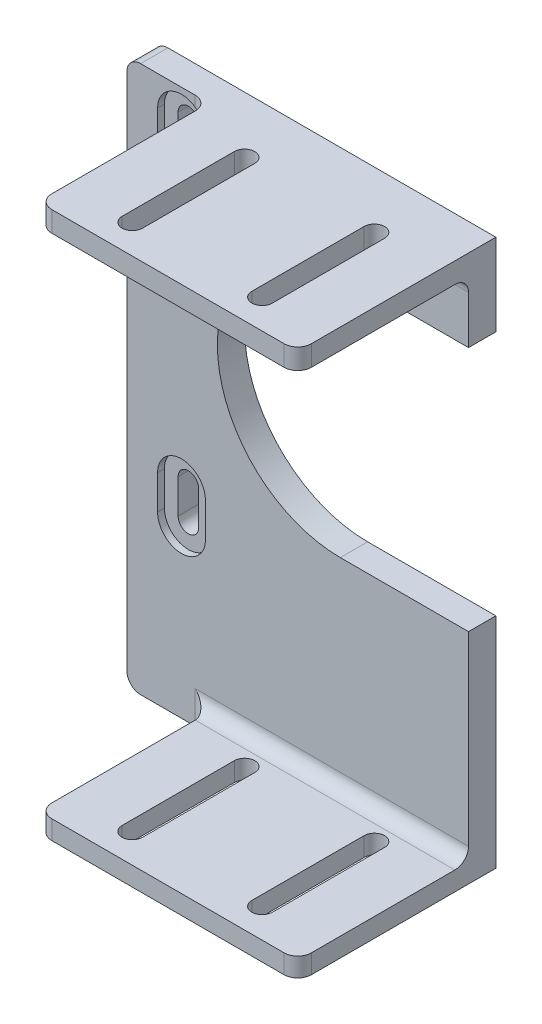
SolidWorks part; units mm, degrees
ref_plane "Front Plane" through (0, 0, 0) normal (0, 0, 1) x (1, 0, 0)
ref_plane "Top Plane" through (0, 0, 0) normal (0, 1, 0) x (1, 0, 0)
ref_plane "Right Plane" through (0, 0, 0) normal (1, 0, 0) x (0, 0, -1)
sketch "Sketch1" plane through (0, 0, 0) normal (0, 0, 1) x (1, 0, 0)
  line L19 (1779.3375, 22.373) -> (1779.3375, -22.3731) construction
  line L20 (1788.3589, -31.3946) -> (1832.7922, -31.3946) construction
  line L21 (1841.8136, -22.3731) -> (1841.8136, 22.373) construction
  line L22 (1832.7922, 31.3944) -> (1788.3589, 31.3944) construction
  line L23 (1853.7515, -14.8225) -> (1846.3832, -11.8988) construction
  line L24 (1779.3375, 22.373) -> (1779.3375, -22.3731) construction
  line L25 (1788.3589, -31.3946) -> (1832.7922, -31.3946) construction
  line L26 (1841.8136, -22.3731) -> (1841.8136, 22.373) construction
  line L27 (1832.7922, 31.3944) -> (1788.3589, 31.3944) construction
  line L28 (1853.7515, -14.8225) -> (1846.3832, -11.8988) construction
  line L29 (1788.3589, -29.8946) -> (1832.7922, -29.8946)
  line L30 (1840.3136, -22.3731) -> (1840.3136, 22.373)
  line L31 (1832.7922, 29.8944) -> (1788.3589, 29.8944)
  line L32 (1829.3375, -18) -> (1829.3375, -29.8946)
  line L33 (1810.5755, 18) -> (1829.3375, 18)
  line L34 (1779.3375, 0) -> (1779.3375, -50)
  line L35 (1779.3375, 0) -> (1829.3375, 0)
  line L36 (1779.3375, -50) -> (1829.3375, -50)
  line L37 (1829.3375, 0) -> (1829.3375, -50)
  line L38 (1810.5755, -18) -> (1829.3375, -18)
  line L39 (1779.3375, 0) -> (1829.3375, 0)
  line L40 (1779.3375, 0) -> (1779.3375, 30)
  line L41 (1779.3375, 30) -> (1829.3375, 30)
  line L42 (1829.3375, 0) -> (1829.3375, 30)
  line L43 (1829.3375, -29.8946) -> (1788.3589, -29.8946)
  arc A10 (1826.4876, 1.6748) -> (1820.1851, -12.7928) centre (1810.5755, 0) ccw construction
  arc A11 (1851.9074, -19.47) -> (1853.7515, -14.8225) centre (1852.8295, -17.1462) ccw construction
  arc A12 (1826.4876, 1.6748) -> (1820.1851, -12.7928) centre (1810.5755, 0) ccw construction
  arc A13 (1851.9074, -19.47) -> (1853.7515, -14.8225) centre (1852.8295, -17.1462) ccw construction
  circle A14 centre (1787.3272, -23.7436) radius 1.5 construction
  circle A15 centre (1787.3272, -23.7436) radius 1.5 construction
  circle A16 centre (1833.8238, -23.7436) radius 1.5 construction
  circle A17 centre (1833.8238, -23.7436) radius 1.5 construction
  circle A18 centre (1833.8238, 23.1061) radius 1.5 construction
  circle A19 centre (1787.3272, 23.1061) radius 1.5
  circle A20 centre (1787.3272, 23.1061) radius 1.5 construction
  circle A21 centre (1833.8238, 23.1061) radius 1.5 construction
  arc A22 (1828.4766, 1.8842) -> (1821.3863, -14.3919) centre (1810.5755, 0) ccw
  parabola Q1 (1842.8609, -10.1768) -> (1826.4876, 1.6748) focus (1827.8677, 2.7392) apex (1826.418, 2.9721) construction
  parabola Q2 (1842.8609, -10.1768) -> (1826.4876, 1.6748) focus (1827.8677, 2.7392) apex (1826.418, 2.9721) construction
  spline S6 degree 3 poles (2125.9154, -960.3929) (1827.9786, 38.5022) (1774.078, -7.1663) (1780.1758, -26.4625) (1781.8315, -28.9006) (1784.2696, -30.5564) (1803.5659, -36.6543) (1849.2336, 17.2492) (850.3625, 315.1978) knots -0.087298 -0.087298 -0.087298 -0.087298 0.347222 0.361111 0.388889 0.416667 0.430556 0.865087 0.865087 0.865087 0.865087 only from (1779.3375, -22.3731) to (1788.3589, -31.3946) construction
  spline S7 degree 3 poles (2770.8029, 315.202) (1771.9171, 17.2497) (1817.5852, -36.6543) (1836.8816, -30.5564) (1839.3196, -28.9006) (1840.9754, -26.4625) (1847.0731, -7.1664) (1793.1728, 38.502) (1495.2376, -960.3866) knots 0.134911 0.134911 0.134911 0.134911 0.569444 0.583333 0.611111 0.638889 0.652778 1.087297 1.087297 1.087297 1.087297 only from (1832.7922, -31.3946) to (1841.8136, -22.3731) construction
  spline S8 degree 3 poles (1495.1659, 960.3676) (1793.1635, -38.5025) (1847.0736, 7.165) (1840.9754, 26.4623) (1839.3196, 28.9004) (1836.8816, 30.5561) (1817.5851, 36.6542) (1771.9171, -17.251) (2770.7955, -315.2292) knots -0.06356 -0.06356 -0.06356 -0.06356 0.805556 0.833333 0.888889 0.944444 0.972222 1.841293 1.841293 1.841293 1.841293 only from (1841.8136, 22.373) to (1832.7922, 31.3944) construction
  spline S9 degree 3 poles (850.3593, -315.2281) (1849.2339, -17.2509) (1803.5661, 36.6542) (1784.2696, 30.5561) (1781.8315, 28.9004) (1780.1758, 26.4623) (1774.0775, 7.165) (1827.9875, -38.5023) (2125.9836, 960.362) knots -0.309535 -0.309535 -0.309535 -0.309535 0.125 0.138889 0.166667 0.194444 0.208333 0.64289 0.64289 0.64289 0.64289 only from (1788.3589, 31.3944) to (1779.3375, 22.373) construction
  spline S10 degree 3 poles (1294.2263, 837.7139) (2450.569, -777.537) (1082.9552, 664.1035) (2665.885, -600.3447) knots -3.232046 -3.232046 -3.232046 -3.232046 3.445011 3.445011 3.445011 3.445011 only from (1820.1851, -12.7928) to (1851.9074, -19.47) construction
  spline S11 degree 3 poles (2833.4468, -172.2254) (835.6889, 37.6788) (2800.9395, 103.594) (867.7165, -231.7317) knots -2.34656 -2.34656 -2.34656 -2.34656 4.307168 4.307168 4.307168 4.307168 only from (1846.3832, -11.8988) to (1842.8609, -10.1768) construction
  spline S12 degree 3 poles (1779.3375, -22.3731) (1779.3375, -22.9801) (1779.4643, -24.2113) (1780.1758, -26.4625) (1781.8315, -28.9006) (1784.2696, -30.5564) (1786.5208, -31.2678) (1787.7519, -31.3946) (1788.3589, -31.3946) knots 0.333333 0.333333 0.333333 0.333333 0.347222 0.361111 0.388889 0.416667 0.430556 0.444444 0.444444 0.444444 0.444444 construction
  spline S13 degree 3 poles (1832.7922, -31.3946) (1833.3992, -31.3946) (1834.6304, -31.2678) (1836.8816, -30.5564) (1839.3196, -28.9006) (1840.9754, -26.4625) (1841.6868, -24.2113) (1841.8136, -22.9801) (1841.8136, -22.3731) knots 0.555556 0.555556 0.555556 0.555556 0.569444 0.583333 0.611111 0.638889 0.652778 0.666667 0.666667 0.666667 0.666667 construction
  spline S14 degree 3 poles (1841.8136, 22.373) (1841.8136, 22.98) (1841.6868, 24.2111) (1840.9754, 26.4623) (1839.3196, 28.9004) (1836.8816, 30.5561) (1834.6304, 31.2676) (1833.3992, 31.3944) (1832.7922, 31.3944) knots 0.777778 0.777778 0.777778 0.777778 0.805556 0.833333 0.888889 0.944444 0.972222 1 1 1 1 construction
  spline S15 degree 3 poles (1788.3589, 31.3944) (1787.7519, 31.3944) (1786.5208, 31.2676) (1784.2696, 30.5561) (1781.8315, 28.9004) (1780.1758, 26.4623) (1779.4643, 24.2111) (1779.3375, 22.98) (1779.3375, 22.373) knots 0.111111 0.111111 0.111111 0.111111 0.125 0.138889 0.166667 0.194444 0.208333 0.222222 0.222222 0.222222 0.222222 construction
  spline S16 degree 3 poles (1820.1851, -12.7928) (1820.9841, -12.2676) (1826.835, -9.5213) (1851.9074, -19.47) knots 0.173188 0.173188 0.173188 0.173188 1.08995 1.08995 1.08995 1.08995 construction
  spline S17 degree 3 poles (1846.3832, -11.8988) (1845.1326, -11.3073) (1843.9601, -10.7333) (1842.8609, -10.1768) knots 0.099174 0.099174 0.099174 0.099174 0.155965 0.155965 0.155965 0.155965 construction
  spline S18 degree 1 poles (1832.7922, -29.8946) (1840.3136, -22.3731) knots 0 0 1 1 construction
  spline S19 degree 1 poles (1840.3136, 22.373) (1832.7922, 29.8944) knots 0 0 1 1 construction
  spline S20 degree 3 poles (1832.7922, -29.8946) (1833.2984, -29.8946) (1834.3274, -29.7881) (1836.1911, -29.1988) (1838.2345, -27.8155) (1839.6178, -25.7721) (1840.2071, -23.9083) (1840.3136, -22.8793) (1840.3136, -22.3731) knots 0.555556 0.555556 0.555556 0.555556 0.569444 0.583333 0.611111 0.638889 0.652778 0.666667 0.666667 0.666667 0.666667
  spline S21 degree 3 poles (1840.3136, 22.373) (1840.3136, 22.8792) (1840.2071, 23.9081) (1839.6178, 25.7719) (1838.2345, 27.8153) (1836.1911, 29.1986) (1834.3274, 29.7879) (1833.2984, 29.8944) (1832.7922, 29.8944) knots 0.777778 0.777778 0.777778 0.777778 0.805556 0.833333 0.888889 0.944444 0.972222 1 1 1 1
  dimension "D4" = 50
  dimension "D5" = 50
  dimension "D6" = 30
  dimension "D1" = 0
  dimension "D2" = 1.5
  dimension "D3" = 2
extrude "Boss-Extrude1" add sketch "Sketch1" along normal blind 4
sketch "Sketch2" plane through (0, 0, 4) normal (0, 0, 1) x (1, 0, 0)
  line L0 (1787.3272, 25.6061) -> (1787.3272, 20.6061) construction
  line L1 (1788.8272, 25.6061) -> (1788.8272, 20.6061)
  line L2 (1785.8272, 25.6061) -> (1785.8272, 20.6061)
  line L3 (1779.3375, 0) -> (1829.3375, 0) construction
  line L4 (1779.3375, 0) -> (1829.3375, 0)
  line L5 (1787.3272, -25.6062) -> (1787.3272, -20.6062) construction
  line L6 (1788.8272, -25.6062) -> (1788.8272, -20.6062)
  line L7 (1785.8272, -25.6062) -> (1785.8272, -20.6062)
  circle A0 centre (1787.3272, -23.7436) radius 1.5 construction
  circle A1 centre (1787.3272, 23.1061) radius 1.5 construction
  circle A2 centre (1787.3272, -23.7436) radius 1.5
  circle A3 centre (1787.3272, 23.1061) radius 1.5 construction
  arc A4 (1788.8272, 25.6061) -> (1785.8272, 25.6061) centre (1787.3272, 25.6061) ccw
  arc A5 (1785.8272, 20.6061) -> (1788.8272, 20.6061) centre (1787.3272, 20.6061) ccw
  arc A6 (1788.8272, -25.6062) -> (1785.8272, -25.6062) centre (1787.3272, -25.6062) cw
  arc A7 (1785.8272, -20.6062) -> (1788.8272, -20.6062) centre (1787.3272, -20.6062) cw
  point P8 (1787.3272, 23.1061)
  point P17 (1787.3272, -23.1062)
  dimension "D1" = 3
  dimension "D2" = 5
extrude "Cut-Extrude2" cut sketch "Sketch2" against normal through all contours L2 A5 L1 A4 | A2 | A6 L6 A2 L7 | A7 L7 A2 L6
sketch "Sketch4" plane through (0, 0, 4) normal (0, 0, 1) x (1, 0, 0)
  line L24 (1779.3375, 0) -> (1829.3375, 0) construction
  line L25 (1779.3375, 0) -> (1829.3375, 0)
  line L26 (1783.8272, 25.6061) -> (1783.8272, 20.6061)
  line L27 (1790.8272, 20.6061) -> (1790.8272, 25.6061)
  line L28 (1783.8272, 25.6061) -> (1783.8272, 20.6061)
  line L29 (1790.8272, 20.6061) -> (1790.8272, 25.6061)
  line L30 (1790.8272, -20.6062) -> (1790.8272, -25.6062)
  line L31 (1783.8272, -25.6062) -> (1783.8272, -20.6062)
  arc A22 (1783.8272, -20.6062) -> (1790.8272, -20.6062) centre (1787.3272, -20.6062) cw
  arc A23 (1790.8272, -25.6062) -> (1783.8272, -25.6062) centre (1787.3272, -25.6062) cw
  arc A24 (1790.8272, 25.6061) -> (1783.8272, 25.6061) centre (1787.3272, 25.6061) ccw
  arc A25 (1783.8272, 20.6061) -> (1790.8272, 20.6061) centre (1787.3272, 20.6061) ccw
  arc A26 (1790.8272, 25.6061) -> (1783.8272, 25.6061) centre (1787.3272, 25.6061) ccw
  arc A27 (1783.8272, 20.6061) -> (1790.8272, 20.6061) centre (1787.3272, 20.6061) ccw
  line M6 (1785.8272, 20.6061) -> (1785.8272, 25.6061)
  arc M7 (1785.8272, 25.6061) -> (1788.8272, 25.6061) centre (1787.3272, 25.6061) cw
  line M8 (1788.8272, 25.6061) -> (1788.8272, 20.6061)
  arc M9 (1788.8272, 20.6061) -> (1785.8272, 20.6061) centre (1787.3272, 20.6061) cw
  line M18 (1788.8272, -20.6062) -> (1788.8272, -25.6062)
  arc M19 (1788.8272, -25.6062) -> (1785.8272, -25.6062) centre (1787.3272, -25.6062) cw
  line M20 (1785.8272, -25.6062) -> (1785.8272, -20.6062)
  arc M21 (1785.8272, -20.6062) -> (1788.8272, -20.6062) centre (1787.3272, -20.6062) cw
  dimension "D1" = 2
extrude "Cut-Extrude3" cut sketch "Sketch4" against normal blind 1 contours L28 A27 L29 A26 M9 M6 M7 M8 | A23 L30 A22 L31 M21 M18 M19 M20
sketch "Sketch6" plane through (0, 30, 0) normal (0, 1, 0) x (1, 0, 0)
  line L1 (1829.3375, -4) -> (1791.3375, -4)
  line L2 (1829.3375, -4) -> (1829.3375, -29)
  line L3 (1829.3375, -29) -> (1791.3375, -29)
  line L4 (1791.3375, -4) -> (1791.3375, -29)
  dimension "D1" = 38
  dimension "D2" = 25
extrude "Boss-Extrude2" add sketch "Sketch6" against normal blind 3
sketch "Sketch7" plane through (0, 0, 4) normal (0, 0, 1) x (1, 0, 0)
  line L0 (1801.5755, 10.1411) -> (1819.5755, 10.1411) construction
  line L1 (1819.5755, 10.1411) -> (1819.5755, 17.1411) construction
  line L2 (1819.5755, 17.1411) -> (1816.8255, 17.1411) construction
  line L3 (1816.8255, 17.1411) -> (1816.8255, 16.0682) construction
  line L4 (1813.8255, 16.0682) -> (1813.8255, 17.1411) construction
  line L5 (1813.8255, 17.1411) -> (1807.3255, 17.1411) construction
  line L6 (1807.3255, 17.1411) -> (1807.3255, 16.0682) construction
  line L7 (1804.3255, 16.0682) -> (1804.3255, 17.1411) construction
  line L8 (1804.3255, 17.1411) -> (1801.5755, 17.1411) construction
  line L9 (1801.5755, 17.1411) -> (1801.5755, 10.1411) construction
  line L10 (1819.5755, -30.3589) -> (1801.5755, -30.3589) construction
  line L11 (1801.5755, -30.3589) -> (1801.5755, -37.3589) construction
  line L12 (1801.5755, -37.3589) -> (1804.3255, -37.3589) construction
  line L13 (1804.3255, -37.3589) -> (1804.3255, -36.2859) construction
  line L14 (1807.3255, -36.2859) -> (1807.3255, -37.3589) construction
  line L15 (1807.3255, -37.3589) -> (1813.8255, -37.3589) construction
  line L16 (1813.8255, -37.3589) -> (1813.8255, -36.2859) construction
  line L17 (1816.8255, -36.2859) -> (1816.8255, -37.3589) construction
  line L18 (1816.8255, -37.3589) -> (1819.5755, -37.3589) construction
  line L19 (1819.5755, -37.3589) -> (1819.5755, -30.3589) construction
  line L20 (1801.5755, 10.1411) -> (1819.5755, 10.1411)
  line L21 (1819.5755, 10.1411) -> (1819.5755, 17.1411)
  line L22 (1819.5755, 17.1411) -> (1816.8255, 17.1411)
  line L23 (1816.8255, 17.1411) -> (1816.8255, 16.0682)
  line L24 (1813.8255, 16.0682) -> (1813.8255, 17.1411)
  line L25 (1813.8255, 17.1411) -> (1807.3255, 17.1411)
  line L26 (1807.3255, 17.1411) -> (1807.3255, 16.0682)
  line L27 (1804.3255, 16.0682) -> (1804.3255, 17.1411)
  line L28 (1804.3255, 17.1411) -> (1801.5755, 17.1411)
  line L29 (1801.5755, 17.1411) -> (1801.5755, 10.1411)
  line L30 (1819.5755, -30.3589) -> (1801.5755, -30.3589)
  line L31 (1801.5755, -30.3589) -> (1801.5755, -37.3589)
  line L32 (1801.5755, -37.3589) -> (1804.3255, -37.3589)
  line L33 (1804.3255, -37.3589) -> (1804.3255, -36.2859)
  line L34 (1807.3255, -36.2859) -> (1807.3255, -37.3589)
  line L35 (1807.3255, -37.3589) -> (1813.8255, -37.3589)
  line L36 (1813.8255, -37.3589) -> (1813.8255, -36.2859)
  line L37 (1816.8255, -36.2859) -> (1816.8255, -37.3589)
  line L38 (1816.8255, -37.3589) -> (1819.5755, -37.3589)
  line L39 (1819.5755, -37.3589) -> (1819.5755, -30.3589)
  line L41 (1801.5755, -37.3589) -> (1801.5755, -47.2189)
  line L42 (1801.5755, 17.1411) -> (1801.5755, 27)
  line L43 (1791.3375, 27) -> (1791.3375, -50.1064)
  line L44 (1829.3375, 30) -> (1791.3375, 30)
  line L45 (1791.3375, 30) -> (1791.3375, 27)
  line L46 (1791.3375, 27) -> (1829.3375, 27)
  line L47 (1829.3375, 27) -> (1829.3375, 30)
  line L48 (1829.3375, 30) -> (1791.3375, 30)
  line L49 (1791.3375, 30) -> (1791.3375, 27)
  line L50 (1791.3375, 27) -> (1829.3375, 27)
  line L51 (1829.3375, 27) -> (1829.3375, 30)
  line L52 (1829.3375, -18) -> (1829.3375, -50) construction
  line L53 (1791.3375, -50.1064) -> (1829.3375, -50.1064)
  line L54 (1791.3375, -50.1064) -> (1791.3375, -47.2189)
  line L55 (1791.3375, -47.2189) -> (1829.3375, -47.2189)
  line L56 (1829.3375, -50.1064) -> (1829.3375, -47.2189)
  arc A0 (1813.8255, 16.0682) -> (1816.8255, 16.0682) centre (1815.3255, 14.3911) ccw construction
  arc A1 (1804.3255, 16.0682) -> (1807.3255, 16.0682) centre (1805.8255, 14.3911) ccw construction
  arc A2 (1807.3255, -36.2859) -> (1804.3255, -36.2859) centre (1805.8255, -34.6089) ccw construction
  arc A3 (1816.8255, -36.2859) -> (1813.8255, -36.2859) centre (1815.3255, -34.6089) ccw construction
  arc A4 (1813.8255, 16.0682) -> (1816.8255, 16.0682) centre (1815.3255, 14.3911) ccw
  arc A5 (1804.3255, 16.0682) -> (1807.3255, 16.0682) centre (1805.8255, 14.3911) ccw
  arc A6 (1807.3255, -36.2859) -> (1804.3255, -36.2859) centre (1805.8255, -34.6089) ccw
  arc A7 (1816.8255, -36.2859) -> (1813.8255, -36.2859) centre (1815.3255, -34.6089) ccw
  line M24 (1779.3375, -50) -> (1829.3375, -50)
  line M25 (1829.3375, -50) -> (1829.3375, -18)
  dimension "D2" = 9.86
  dimension "D1" = 0
extrude "Boss-Extrude3" add sketch "Sketch7" along normal up to surface (25 mm away) contours L55 L43 M24 M25 up to face at (1810.3375, 28.5, 29)
sketch "Sketch8" plane through (0, -50.0001, 0) normal (0, -1, 0) x (1, 0, 0)
  line L0 (1791.3375, 16.5) -> (1829.3375, 16.5)
  line L1 (1791.3375, 29) -> (1791.3375, 4) construction
  line L2 (1829.3375, 29) -> (1829.3375, 0) construction
  line L3 (1810.3375, 16.5) -> (1791.3375, 16.5)
  line L4 (1800.8375, 8.286) -> (1800.8375, 24.714) construction
  line L5 (1799.3375, 8.286) -> (1799.3375, 24.714)
  line L6 (1802.3375, 8.286) -> (1802.3375, 24.714)
  line L7 (1810.3375, 16.5) -> (1810.3375, 26.309)
  line L8 (1819.8375, 8.286) -> (1819.8375, 24.714) construction
  line L9 (1821.3375, 8.286) -> (1821.3375, 24.714)
  line L10 (1818.3375, 8.286) -> (1818.3375, 24.714)
  arc A0 (1799.3375, 8.286) -> (1802.3375, 8.286) centre (1800.8375, 8.286) ccw
  arc A1 (1802.3375, 24.714) -> (1799.3375, 24.714) centre (1800.8375, 24.714) ccw
  arc A2 (1821.3375, 8.286) -> (1818.3375, 8.286) centre (1819.8375, 8.286) cw
  arc A3 (1818.3375, 24.714) -> (1821.3375, 24.714) centre (1819.8375, 24.714) cw
  point P9 (1800.8375, 16.5)
  point P17 (1819.8375, 16.5)
  dimension "D1" = 3
extrude "Cut-Extrude4" cut sketch "Sketch8" against normal through all contours L6 A1 L5 L3 | A3 L10 L0 L9 | A2 L9 L0 L10
fillet "Fillet1" radius 2 4 edges at (1791.3375, 28.5, 4) (1791.3375, -48.6095, 4) (1810.3375, -47.2189, 4) (1810.3375, 27, 4)
fillet "Fillet2" radius 2 6 edges at (1779.3375, 30, 2) (1779.3375, -50, 2) (1829.3375, -48.6095, 29) (1791.3375, -48.6095, 29) (1829.3375, 28.5, 29) (1791.3375, 28.5, 29)
equation "\"2mmm\"=0.5"
